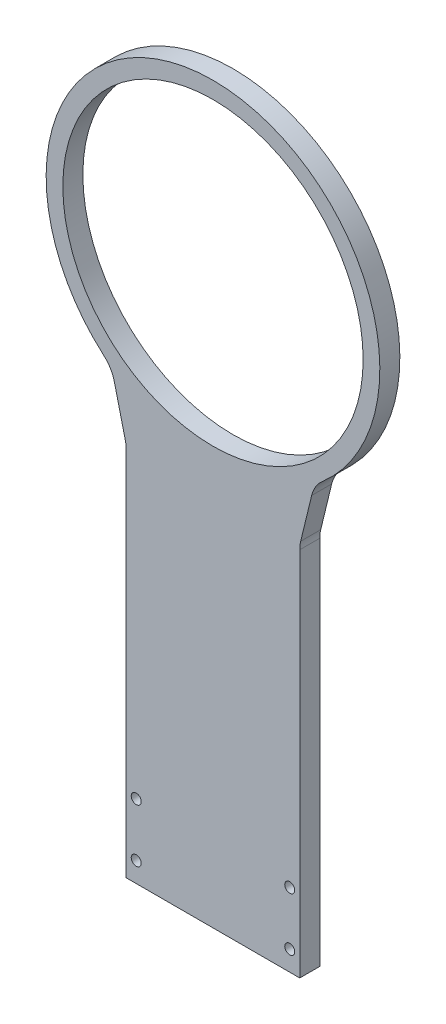
SolidWorks part; units mm, degrees
ref_plane "Front" through (0, 0, 0) normal (0, 0, 1) x (1, 0, 0)
ref_plane "Top" through (0, 0, 0) normal (0, 1, 0) x (1, 0, 0)
ref_plane "Right" through (0, 0, 0) normal (1, 0, 0) x (0, 0, -1)
sketch "Esquisse1" plane through (0, 0, 0) normal (0, 0, 1) x (1, 0, 0)
  line L1 (0, 0) -> (100, 0)
  line L2 (0, 0) -> (0, 100)
  line L3 (0, 100) -> (100, 100)
  line L4 (100, 0) -> (100, 100)
  dimension "D1" = 100
  dimension "D2" = 100
extrude "Boss.-Extru.1" add sketch "Esquisse1" along normal blind 6
sketch "Esquisse2" plane through (0, 0, 6) normal (0, 0, 1) x (1, 0, 0)
  line L1 (50, 0) -> (50, 100) construction
  line L2 (0, 0) -> (100, 0) construction
  line L3 (100, 100) -> (0, 100) construction
  circle A0 centre (50, 50) radius 45
  dimension "D1" = 90
extrude "Enlèv. mat.-Extru.1" cut sketch "Esquisse2" against normal through all
sketch "Esquisse3" plane through (0, 0, 6) normal (0, 0, 1) x (1, 0, 0)
  line L0 (100, 0) -> (100, 100) construction
  line L1 (0, 0) -> (100, 0)
  line L2 (0, 0) -> (0, -120)
  line L3 (0, -120) -> (100, -120)
  line L4 (100, 0) -> (100, -120)
  dimension "D1" = 120
extrude "Boss.-Extru.2" add sketch "Esquisse3" against normal up to vertex (6 mm away) up to point (100, 0, 0)
sketch "Esquisse4" plane through (0, 0, 6) normal (0, 0, 1) x (1, 0, 0)
  line L0 (50, -120) -> (50, -3.3563) construction
  line L1 (0, -120) -> (100, -120) construction
  line L2 (0, 100) -> (0, -120) construction
  line L3 (24, -120) -> (0, -120)
  line L4 (24, -120) -> (24, 0)
  line L5 (24, 0) -> (0, 0)
  line L6 (0, -120) -> (0, 0)
  line L7 (100, -120) -> (100, 0)
  line L8 (76, 0) -> (100, 0)
  line L9 (76, -120) -> (76, 0)
  line L10 (76, -120) -> (100, -120)
  dimension "D1" = 52
  dimension "D2" = 120
extrude "Enlèv. mat.-Extru.2" cut sketch "Esquisse4" against normal up to vertex (126 mm away) up to point (0, 100, -120)
sketch "Esquisse5" plane through (0, 0, 6) normal (0, 0, 1) x (1, 0, 0)
  line L0 (50, -120) -> (50, -10.2588) construction
  line L1 (24, -120) -> (76, -120) construction
  line L2 (27, -120) -> (27, -98) construction
  line L3 (24, -120) -> (24, 0) construction
  circle A0 centre (27, -98) radius 1.5
  circle A1 centre (27, -114) radius 1.5
  circle A2 centre (73, -114) radius 1.5
  circle A3 centre (73, -98) radius 1.5
  dimension "D1" = 16
  dimension "D2" = 6
  dimension "D4" = 3
  dimension "D3" = 3
extrude "Enlèv. mat.-Extru.3" cut sketch "Esquisse5" against normal through all
sketch "Esquisse6" plane through (0, 0, 6) normal (0, 0, 1) x (1, 0, 0)
  line L0 (76, 7.2917) -> (76, 0)
  line L1 (24, 0) -> (24, 7.2917)
  line L2 (100, 0) -> (100, 100) construction
  line L3 (24, 0) -> (-1, 0)
  line L4 (-1, 0) -> (-1, 101)
  line L5 (50, 50) -> (50, 80.2211) construction
  line L6 (50, 80.2211) -> (50, 101) construction
  line L7 (-1, 101) -> (101, 101)
  line L8 (100, 100) -> (0, 100) construction
  line L9 (0, 100) -> (0, 0) construction
  line L10 (76, 0) -> (101, 0)
  line L11 (101, 0) -> (101, 101)
  arc A0 (24, 7.2917) -> (76, 7.2917) centre (50, 50) cw
  dimension "D1" = 1
  dimension "D2" = 1
extrude "Enlèv. mat.-Extru.4" cut sketch "Esquisse6" against normal through all
chamfer "Chanfrein1" distance 5 angle 45 2 edges at (24, 7.2917, 3) (76, 7.2917, 3) first distance on face at (50, 53.6458, 3)
fillet "Congé1" radius 10 4 edges at (19.6358, 10.2758, 3) (24, -7.6709, 3) (76, -7.6709, 3) (80.3642, 10.2758, 3)
